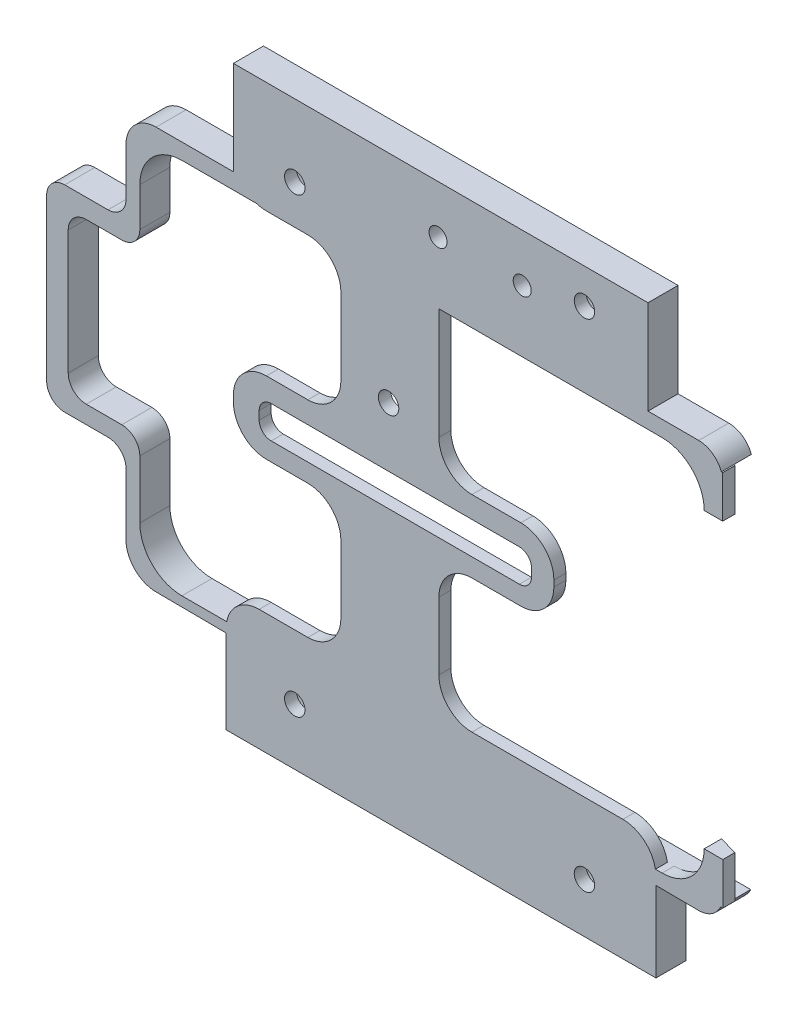
SolidWorks part; units mm, degrees
ref_plane "Plan de face" through (0, 0, 0) normal (0, 0, 1) x (1, 0, 0)
ref_plane "Plan de dessus" through (0, 0, 0) normal (0, 1, 0) x (1, 0, 0)
ref_plane "Plan de droite" through (0, 0, 0) normal (1, 0, 0) x (0, 0, -1)
sketch "Esquisse1" plane through (0, 0, 0) normal (0, 0, 1) x (1, 0, 0)
  line L0 (-101.8864, 22.7193) -> (-64.9263, 22.7193) construction
  line L1 (-68.0864, 83.4017) -> (-68.0864, 71.4017) construction
  line L2 (-118.8906, -27.2807) -> (-47.3665, -27.2807) construction
  line L3 (-120.7144, 72.7193) -> (-45.5428, 72.7193) construction
  line L4 (-83.4864, -42.5983) -> (-83.4864, 89.4017) construction
  line L5 (-56.8564, -27.2807) -> (-56.8564, 72.7193) construction
  line L6 (-110.1164, -27.2807) -> (-110.1164, 72.7193) construction
  line L7 (-59.2664, -27.2807) -> (-59.2664, 72.7193) construction
  line L8 (-56.8564, -13.2807) -> (-110.1164, -13.2807) construction
  line L9 (-64.3564, -27.2807) -> (-64.3564, 72.7193) construction
  line L10 (-110.1164, 36.7193) -> (-56.8564, 36.7193) construction
  line L11 (-56.8564, 66.9393) -> (-110.1164, 66.9393) construction
  line L12 (-91.8564, -27.2807) -> (-91.8564, 72.7193) construction
  line L13 (-107.4664, -27.2807) -> (-107.4664, 72.7193) construction
  line L14 (-56.8564, -14.5207) -> (-110.1164, -14.5207) construction
  line L15 (-110.1164, 60.7193) -> (-56.8564, 60.7193) construction
  line L16 (-117.6801, 66.9393) -> (-117.6801, 59.6951)
  line L17 (-112.1801, 54.1951) -> (-105.2942, 54.1951)
  line L18 (-99.7942, 48.6951) -> (-99.7942, 35.9308)
  line L20 (-105.2942, -3.8078) -> (-113.3906, -3.8078)
  line L21 (-118.8906, -9.3078) -> (-118.8906, -18.422)
  line L22 (-113.3906, -23.922) -> (-52.8665, -23.922)
  line L23 (-47.3665, -18.422) -> (-47.3665, -9.3078)
  line L24 (-52.8665, -3.8078) -> (-77.9864, -3.8078)
  line L25 (-83.4864, 1.6922) -> (-83.4864, 12.91)
  line L26 (-77.9864, 60.7193) -> (-54.1904, 60.7193)
  line L27 (-48.6904, 66.2193) -> (-48.6904, 67.2193)
  line L28 (-54.1904, 72.7193) -> (-112.1801, 72.7193)
  line L29 (-117.6801, 67.2193) -> (-117.6801, 66.9393)
  line L30 (-105.2942, 30.4308) -> (-112.1801, 30.4308)
  line L31 (-117.6801, 24.9308) -> (-117.6801, 23.91)
  line L32 (-112.1801, 18.41) -> (-105.2942, 18.41)
  line L33 (-77.9864, 30.4308) -> (-69.8564, 30.4308)
  line L34 (-64.3564, 24.9308) -> (-64.3564, 23.91)
  line L35 (-69.8564, 18.41) -> (-77.9864, 18.41)
  line L36 (-99.7942, 12.91) -> (-99.7942, 1.6922)
  line L37 (-111.3906, 21.4601) -> (-70.0864, 21.4601)
  line L38 (-113.3906, 23.4601) -> (-113.3906, 24.8425)
  line L39 (-111.3906, 26.8425) -> (-70.0864, 26.8425)
  line L40 (-68.0864, 23.4601) -> (-68.0864, 24.8425)
  line L41 (-83.4864, 35.9308) -> (-83.4864, 55.2193)
  circle A0 centre (-59.2664, -15.6637) radius 1.7
  arc A1 (-77.9864, 30.4308) -> (-83.4864, 35.9308) centre (-77.9864, 35.9308) cw
  circle A2 centre (-59.2664, 66.9393) radius 1.7
  circle A3 centre (-91.8564, 36.7193) radius 1.7
  arc A4 (-64.3564, 23.91) -> (-69.8564, 18.41) centre (-69.8564, 23.91) cw
  arc A5 (-112.1801, 72.7193) -> (-117.6801, 67.2193) centre (-112.1801, 67.2193) ccw
  circle A6 centre (-107.4664, -14.5207) radius 1.7
  circle A7 centre (-107.4664, 60.7193) radius 1.7
  arc A8 (-117.6801, 59.6951) -> (-112.1801, 54.1951) centre (-112.1801, 59.6951) ccw
  arc A9 (-105.2942, 54.1951) -> (-99.7942, 48.6951) centre (-105.2942, 48.6951) cw
  arc A10 (-99.7942, 1.6922) -> (-105.2942, -3.8078) centre (-105.2942, 1.6922) cw
  arc A11 (-113.3906, -3.8078) -> (-118.8906, -9.3078) centre (-113.3906, -9.3078) ccw
  arc A12 (-118.8906, -18.422) -> (-113.3906, -23.922) centre (-113.3906, -18.422) ccw
  arc A13 (-52.8665, -23.922) -> (-47.3665, -18.422) centre (-52.8665, -18.422) ccw
  arc A14 (-47.3665, -9.3078) -> (-52.8665, -3.8078) centre (-52.8665, -9.3078) ccw
  arc A15 (-77.9864, -3.8078) -> (-83.4864, 1.6922) centre (-77.9864, 1.6922) cw
  arc A16 (-83.4864, 55.2193) -> (-77.9864, 60.7193) centre (-77.9864, 55.2193) cw
  arc A17 (-54.1904, 60.7193) -> (-48.6904, 66.2193) centre (-54.1904, 66.2193) ccw
  arc A18 (-48.6904, 67.2193) -> (-54.1904, 72.7193) centre (-54.1904, 67.2193) ccw
  arc A19 (-69.8564, 30.4308) -> (-64.3564, 24.9308) centre (-69.8564, 24.9308) cw
  arc A20 (-77.9864, 18.41) -> (-83.4864, 12.91) centre (-77.9864, 12.91) ccw
  arc A21 (-105.2942, 18.41) -> (-99.7942, 12.91) centre (-105.2942, 12.91) cw
  arc A22 (-117.6801, 23.91) -> (-112.1801, 18.41) centre (-112.1801, 23.91) ccw
  arc A23 (-112.1801, 30.4308) -> (-117.6801, 24.9308) centre (-112.1801, 24.9308) ccw
  arc A24 (-105.2942, 30.4308) -> (-99.7942, 35.9308) centre (-105.2942, 35.9308) ccw
  arc A25 (-70.0864, 26.8425) -> (-68.0864, 24.8425) centre (-70.0864, 24.8425) cw
  arc A26 (-70.0864, 21.4601) -> (-68.0864, 23.4601) centre (-70.0864, 23.4601) ccw
  arc A27 (-111.3906, 21.4601) -> (-113.3906, 23.4601) centre (-111.3906, 23.4601) cw
  arc A28 (-113.3906, 24.8425) -> (-111.3906, 26.8425) centre (-111.3906, 24.8425) cw
  point P61 (-117.6801, 72.7193)
  point P68 (-99.7942, -3.8078)
  point P79 (-83.4864, -3.8078)
  point P82 (-83.4864, 60.7193)
  point P87 (-48.6904, 72.7193)
  point P98 (-83.4864, 30.4308)
  point P101 (-64.3564, 18.41)
  point P104 (-64.3564, 30.4308)
  point P109 (-99.7942, 18.41)
  point P116 (-99.7942, 30.4308)
  dimension "D1" = 5.5
  dimension "D2" = 5.5
  dimension "D3" = 2
extrude "Boss.-Extru.1" add sketch "Esquisse1" along normal blind 3
sketch "Esquisse2" plane through (0, 0, 0) normal (0, 0, -1) x (-1, 0, 0)
  line L0 (39.3464, 87.1044) -> (39.3464, -42.3137) construction
  line L1 (133.2464, 87.1044) -> (133.2464, 37.9772) construction
  line L2 (59.2664, -15.6637) -> (59.2664, 1.7249) construction
  line L3 (133.2464, -8.2937) -> (39.3464, -8.2937) construction
  line L4 (133.2464, 54.4563) -> (39.3464, 54.4563) construction
  line L5 (126.2464, -8.2937) -> (126.2464, -1.2937) construction
  line L6 (126.2464, -1.2937) -> (133.2464, -1.2937) construction
  line L7 (126.2464, 54.4563) -> (126.2464, 47.4563) construction
  line L8 (126.2464, 47.4563) -> (133.2464, 47.4563) construction
  line L9 (46.3464, 54.4563) -> (46.3464, 47.4563) construction
  line L10 (46.3464, 47.4563) -> (39.3464, 47.4563) construction
  line L11 (39.3464, -1.2937) -> (46.3464, -1.2937) construction
  line L12 (46.3464, -1.2937) -> (46.3464, -8.2937) construction
  line L13 (118.8906, -9.9695) -> (130.5846, -9.8801)
  line L14 (117.6801, 57.0999) -> (130.5464, 57.0999)
  line L15 (47.3665, -10.5841) -> (47.3665, -23.922)
  line L16 (36.2569, 53.0999) -> (36.2569, 47.4563)
  line L17 (36.2569, 47.4563) -> (39.3464, 47.4563)
  line L18 (39.3464, -1.2937) -> (36.2482, -1.2937)
  line L19 (36.2482, -1.2937) -> (36.2482, -6.6454)
  line L20 (40.2828, -10.6453) -> (47.3665, -10.5841)
  line L21 (48.6904, 60.7193) -> (48.6904, 72.7193)
  line L22 (48.6904, 60.7193) -> (48.6904, 57.0999)
  line L23 (126.2464, 54.4563) -> (46.3464, 54.4563)
  line L24 (46.3464, -8.2937) -> (126.2464, -8.2937)
  line L25 (133.2464, 47.4563) -> (133.2464, 40.9772)
  line L26 (48.6904, 72.7193) -> (117.6801, 72.7193)
  line L27 (138.5464, 8.4156) -> (145.7527, 8.4156)
  line L28 (40.2569, 57.0999) -> (48.6904, 57.0999)
  line L29 (148.7527, 11.4156) -> (148.7527, 38.1792)
  line L30 (133.2464, 34.4495) -> (133.2464, -42.3137) construction
  line L32 (117.6801, 72.7193) -> (117.6801, 57.0999)
  line L35 (135.5464, -24.0475) -> (135.5464, 64.4693) construction
  line L36 (47.3665, -18.422) -> (47.3665, -9.3078) construction
  line L37 (133.2464, 8.3631) -> (133.2464, -1.2937)
  line L38 (47.3665, -23.922) -> (118.8906, -23.922)
  line L39 (118.8906, -23.922) -> (118.8906, -9.9695)
  line L40 (118.8906, -9.3078) -> (118.8906, -18.422) construction
  line L41 (145.7527, 41.1792) -> (138.5464, 41.1792)
  line L42 (136.2464, 11.3631) -> (142.1623, 11.3631)
  line L43 (145.1623, 14.3631) -> (145.1623, 34.9772)
  line L44 (142.1623, 37.9772) -> (136.2464, 37.9772)
  line L47 (135.5464, -4.8802) -> (135.5464, 5.4156)
  line L57 (135.5464, 44.1792) -> (135.5464, 52.0999)
  arc A0 (133.2464, -1.2937) -> (126.2464, -8.2937) centre (126.2464, -1.2937) cw
  arc A1 (133.2464, 47.4563) -> (126.2464, 54.4563) centre (126.2464, 47.4563) ccw
  arc A2 (46.3464, 54.4563) -> (39.3464, 47.4563) centre (46.3464, 47.4563) ccw
  arc A3 (39.3464, -1.2937) -> (46.3464, -8.2937) centre (46.3464, -1.2937) ccw
  arc A4 (40.2569, 57.0999) -> (36.2569, 53.0999) centre (40.2569, 53.0999) ccw
  arc A5 (148.7527, 38.1792) -> (145.7527, 41.1792) centre (145.7527, 38.1792) ccw
  arc A6 (138.5464, 41.1792) -> (135.5464, 44.1792) centre (138.5464, 44.1792) cw
  arc A7 (136.2464, 37.9772) -> (133.2464, 40.9772) centre (136.2464, 40.9772) cw
  arc A8 (145.1623, 34.9772) -> (142.1623, 37.9772) centre (142.1623, 34.9772) ccw
  arc A9 (142.1623, 11.3631) -> (145.1623, 14.3631) centre (142.1623, 14.3631) ccw
  arc A10 (145.7527, 8.4156) -> (148.7527, 11.4156) centre (145.7527, 11.4156) ccw
  arc A11 (133.2464, 8.3631) -> (136.2464, 11.3631) centre (136.2464, 8.3631) cw
  arc A12 (135.5464, 52.0999) -> (130.5464, 57.0999) centre (130.5464, 52.0999) ccw
  arc A13 (138.5464, 8.4156) -> (135.5464, 5.4156) centre (138.5464, 5.4156) ccw
  arc A15 (130.5846, -9.8801) -> (135.5464, -4.8802) centre (130.5464, -4.8802) ccw
  arc A16 (36.2482, -6.6454) -> (40.2828, -10.6453) centre (40.2482, -6.6454) ccw
  circle A17 centre (59.2664, -15.6637) radius 5.2
  circle A18 centre (107.4664, -14.5207) radius 5.2
  circle A19 centre (107.4664, 60.7193) radius 5.2
  circle A20 centre (59.2664, 66.9393) radius 5.2
  point P34 (135.5464, 57.0999)
  point P37 (132.9964, 22.9063)
  point P43 (132.9964, 22.9063)
  point P45 (133.2464, 29.4495)
  point P50 (133.2464, 16.3631)
  point P62 (111.5444, -10.0296)
  point P71 (64.0892, -10.4396)
  point P74 (135.5464, 26.097)
  point P75 (134.7715, 19.7156)
  point P107 (135.5464, 19.7156)
  point P110 (135.5464, -9.8421)
  dimension "D13" = 4
  dimension "D14" = 3
  dimension "D16" = 5
  dimension "D1" = 19.92
  dimension "D2" = 93.9
  dimension "D3" = 7.37
  dimension "D4" = 62.75
  dimension "D5" = 7
  dimension "D6" = 7
  dimension "D7" = 7
  dimension "D8" = 7
  dimension "D9" = 7
  dimension "D10" = 7
  dimension "D11" = 7
  dimension "D12" = 7
  dimension "D17" = 2.3
extrude "Boss.-Extru.2" add sketch "Esquisse2" along normal blind 3 and the other way blind 3
sketch "Esquisse5" plane through (0, 0, 3) normal (0, 0, 1) x (1, 0, 0)
  line L1 (-156.3908, -30.1977) -> (-27.0007, -30.1977)
  line L2 (-156.3908, -30.1977) -> (-156.3908, 79.8705)
  line L3 (-156.3908, 79.8705) -> (-27.0007, 79.8705)
  line L4 (-27.0007, -30.1977) -> (-27.0007, 79.8705)
extrude "Enlèv. mat.-Extru.2" cut sketch "Esquisse5" against normal blind 1
sketch "Esquisse6" plane through (0, 0, 2) normal (0, 0, 1) x (1, 0, 0)
  line L0 (-69.6235, 64.7274) -> (-83.6235, 64.7274) construction
  circle A0 centre (-69.6235, 64.7274) radius 1.5
  circle A1 centre (-83.6235, 64.7274) radius 1.5
extrude "Enlèv. mat.-Extru.3" cut sketch "Esquisse6" against normal blind 8
sketch "Esquisse7" plane through (0, 0, 0) normal (0, 0, -1) x (-1, 0, 0)
  line L0 (47.4608, -8.2937) -> (118.7963, -8.2937) construction
  line L1 (49.8731, -8.2937) -> (35.2624, -8.2937)
  line L2 (49.8731, -8.2937) -> (49.8731, 54.4563)
  line L3 (49.8731, 54.4563) -> (35.2624, 54.4563)
  line L4 (35.2624, -8.2937) -> (35.2624, 54.4563)
  line L5 (113.8548, 54.4563) -> (83.4864, 54.4563) construction
extrude "Enlèv. mat.-Extru.4" cut sketch "Esquisse7" along normal blind 8
sketch "Esquisse9" plane through (0, -1.2937, 0) normal (0, 1, 0) x (1, 0, 0)
  line L0 (-39.3464, -2) -> (-39.3464, 0.886)
  line L1 (-39.3464, 0.886) -> (-36.2482, 0)
  line L2 (-36.2482, 0) -> (-36.2482, -2)
  line L3 (-36.2482, -2) -> (-39.3464, -2)
extrude "Boss.-Extru.3" add sketch "Esquisse9" against normal blind 7
sketch "Esquisse10" plane through (0, 47.4563, 0) normal (0, -1, 0) x (1, 0, 0)
  line L0 (-39.3464, 2) -> (-39.3464, -0.873)
  line L1 (-39.3464, -0.873) -> (-36.2569, 0)
  line L2 (-36.2569, 0) -> (-36.2569, 2)
  line L3 (-36.2569, 2) -> (-39.3464, 2)
extrude "Boss.-Extru.4" add sketch "Esquisse10" against normal blind 7
